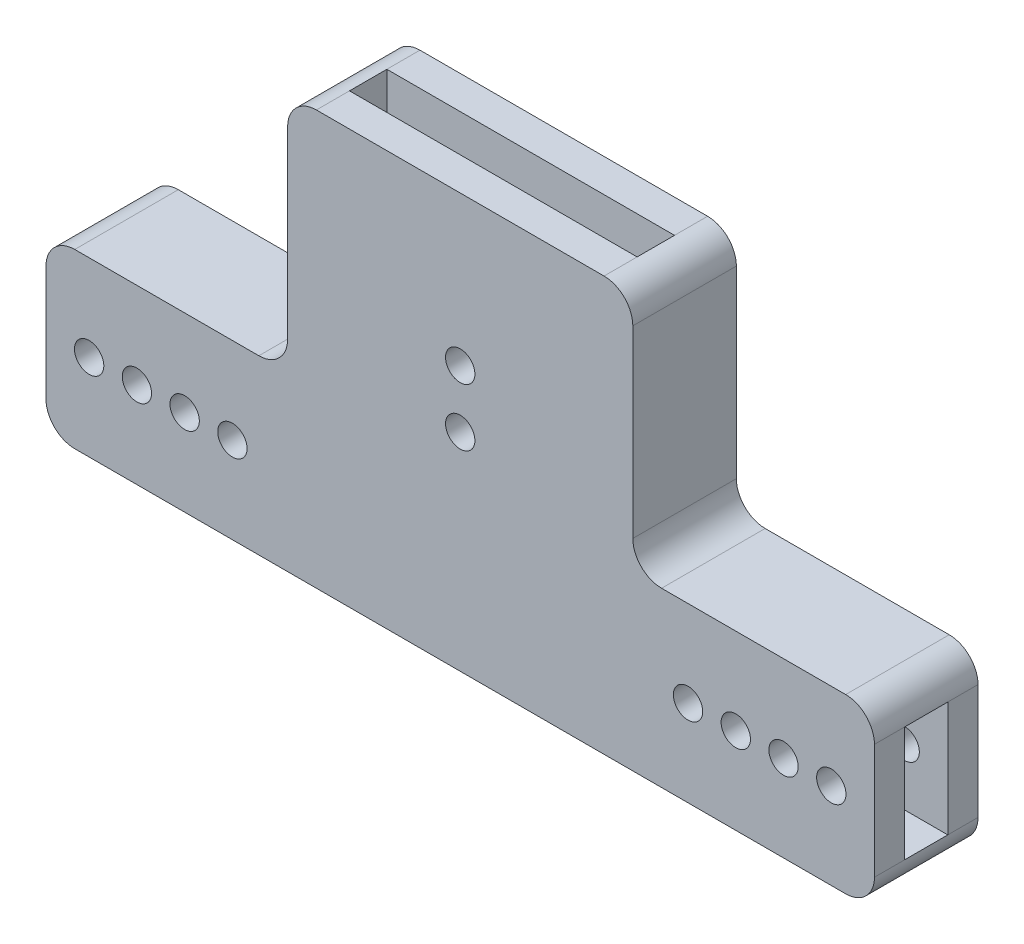
SolidWorks part; units mm, degrees
ref_plane "Front Plane" through (0, 0, 0) normal (0, 0, 1) x (1, 0, 0)
ref_plane "Top Plane" through (0, 0, 0) normal (0, 1, 0) x (1, 0, 0)
ref_plane "Right Plane" through (0, 0, 0) normal (1, 0, 0) x (0, 0, -1)
sketch "Sketch1" plane through (0, 0, 0) normal (0, 0, 1) x (1, 0, 0)
  line L1 (-30, 36) -> (30, 36)
  line L2 (-30, 36) -> (-30, -36)
  line L3 (-30, -36) -> (30, -36)
  line L4 (30, 36) -> (30, -36)
  line L5 (-30, 36) -> (30, -36) construction
  line L6 (-30, -36) -> (30, 36) construction
  point P0 (0, 0)
  dimension "D1" = 60
  dimension "D2" = 72
extrude "Boss-Extrude1" add sketch "Sketch1" along normal blind 18
sketch "Sketch2" plane through (0, 36, 0) normal (0, 1, 0) x (1, 0, 0)
  line L0 (0, 0) -> (0, -18) construction
  line L1 (-25, -5.75) -> (25, -5.75)
  line L2 (-25, -5.75) -> (-25, -12.25)
  line L3 (-25, -12.25) -> (25, -12.25)
  line L4 (25, -5.75) -> (25, -12.25)
  line L5 (-25, -5.75) -> (25, -12.25) construction
  line L6 (-25, -12.25) -> (25, -5.75) construction
  line L7 (30, 0) -> (-30, 0) construction
  line L8 (-30, -9) -> (30, -9) construction
  line L9 (-30, -18) -> (-30, 0) construction
  line L10 (30, -18) -> (30, 0) construction
  line L11 (30, -18) -> (-30, -18) construction
  point P0 (0, -9)
  dimension "D2" = 6.5
  dimension "D3" = 50
extrude "Cut-Extrude1" cut sketch "Sketch2" against normal through all
sketch "Sketch3" plane through (-30, 0, 0) normal (-1, 0, 0) x (0, 0, 1)
  line L0 (18, 36) -> (18, -36) construction
  line L1 (0, -36) -> (18, -36)
  line L2 (0, -36) -> (0, -6)
  line L3 (0, -6) -> (18, -6)
  line L4 (18, -36) -> (18, -6)
  line L5 (9, -6) -> (9, -36) construction
  line L6 (0, -21) -> (18, -21) construction
  point P1024 (9, -21)
  dimension "D1" = 30
extrude "Boss-Extrude2" add sketch "Sketch3" along normal blind 42
sketch "Sketch4" plane through (-72, 0, 0) normal (-1, 0, 0) x (0, 0, 1)
  line L0 (18, -6) -> (0, -6) construction
  line L1 (5.25, -11) -> (12.75, -11)
  line L2 (5.25, -11) -> (5.25, -31)
  line L3 (5.25, -31) -> (12.75, -31)
  line L4 (12.75, -11) -> (12.75, -31)
  line L5 (5.25, -11) -> (12.75, -31) construction
  line L6 (5.25, -31) -> (12.75, -11) construction
  line L9 (0, -36) -> (18, -36) construction
  line L10 (9, -6) -> (9, -36) construction
  point P0 (9, -21)
  dimension "D1" = 5
  dimension "D3" = 7.5
extrude "Cut-Extrude2" cut sketch "Sketch4" against normal blind 42.5
sketch "Sketch5" plane through (0, 0, 18) normal (0, 0, 1) x (1, 0, 0)
  line L0 (-72, -11) -> (-72, -31) construction
  line L2 (-72, -6) -> (-30, -6) construction
  circle A0 centre (-64.5, -21) radius 2.55
  circle A1 centre (-56.2, -21) radius 2.55
  circle A2 centre (-47.9, -21) radius 2.55
  circle A3 centre (-39.6, -21) radius 2.55
  dimension "D1" = 4
  dimension "D3" = 5.1
  dimension "D2" = 7.5
  dimension "D4" = 15
  dimension "D5" = 8.3
extrude "Cut-Extrude3" cut sketch "Sketch5" against normal blind 35
mirror "Mirror1" about plane through (0, 0, 0) normal (1, 0, 0) of "Cut-Extrude3", "Cut-Extrude2", "Boss-Extrude2"
fillet "Fillet1" radius 5 8 edges at (72, -36, 9) (72, -6, 9) (30, -6, 9) (-72, -36, 9) (-72, -6, 9) (-30, -6, 9) (30, 36, 9) (-30, 36, 9)
sketch "Sketch6" plane through (0, 0, 18) normal (0, 0, 1) x (1, 0, 0)
  circle A0 centre (0, 0) radius 2.55
  circle A1 centre (0, 10) radius 2.55
  dimension "D1" = 10
extrude "Cut-Extrude4" cut sketch "Sketch6" against normal blind 35
